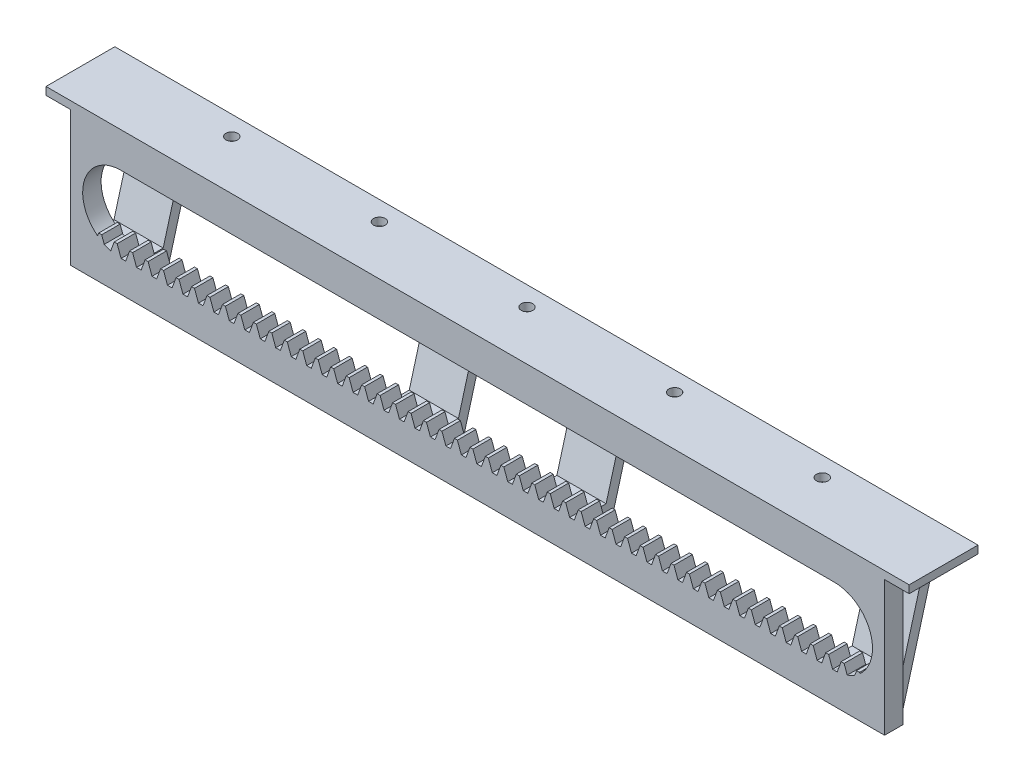
SolidWorks part; units mm, degrees
material "Nylon 101"
ref_plane "Front Plane" through (0, 0, 0) normal (0, 0, 1) x (1, 0, 0)
ref_plane "Top Plane" through (0, 0, 0) normal (0, 1, 0) x (1, 0, 0)
ref_plane "Right Plane" through (0, 0, 0) normal (1, 0, 0) x (0, 0, -1)
sketch "Sketch1" plane through (0, 0, 0) normal (0, 1, 0) x (1, 0, 0)
  line L0 (0, 0) -> (0, 4.7625)
  line L1 (0, 4.7625) -> (203.2, 4.7625)
  line L2 (203.2, 4.7625) -> (203.2, 0)
  line L3 (203.2, 0) -> (0, 0)
  dimension "D1" = 4.7625
  dimension "D2" = 203.2
extrude "Boss-Extrude1" add sketch "Sketch1" along normal blind 4.5
sketch "Sketch2" plane through (0, 0, 0) normal (0, 0, 1) x (1, 0, 0)
  line L0 (0, 3.2275) -> (203.2, 3.2275) construction
  line L1 (0, 4.5) -> (0, 0) construction
  line L2 (203.2, 4.5) -> (203.2, 0) construction
  line L3 (0, 1.7035) -> (203.2, 1.7035) construction
  line L4 (0, 4.5) -> (203.2, 4.5) construction
  line L5 (0, 4.5) -> (0.5952, 4.5) construction
  line L6 (0.5952, 4.5) -> (1.613, 1.7035)
  line L7 (1.613, 1.7035) -> (2.2082, 1.7035)
  line L8 (2.8034, 1.7035) -> (3.8212, 4.5)
  line L9 (3.8212, 4.5) -> (4.4164, 4.5) construction
  line L10 (2.2082, 1.7035) -> (2.8034, 1.7035)
  line L11 (0.5952, 4.5) -> (3.8212, 4.5)
  line L12 (4.5868, 4.5) -> (5.6047, 1.7035)
  line L13 (5.6047, 1.7035) -> (6.1999, 1.7035)
  line L14 (6.795, 1.7035) -> (7.8129, 4.5)
  line L15 (6.1999, 1.7035) -> (6.795, 1.7035)
  line L16 (4.5868, 4.5) -> (7.8129, 4.5)
  line L17 (3.9917, 4.5) -> (4.5868, 4.5) construction
  line L18 (7.8129, 4.5) -> (8.4081, 4.5) construction
  line L19 (8.5785, 4.5) -> (9.5964, 1.7035)
  line L20 (9.5964, 1.7035) -> (10.1915, 1.7035)
  line L21 (10.7867, 1.7035) -> (11.8046, 4.5)
  line L22 (10.1915, 1.7035) -> (10.7867, 1.7035)
  line L23 (8.5785, 4.5) -> (11.8046, 4.5)
  line L24 (7.9834, 4.5) -> (8.5785, 4.5) construction
  line L25 (11.8046, 4.5) -> (12.3997, 4.5) construction
  line L26 (12.5702, 4.5) -> (13.5881, 1.7035)
  line L27 (13.5881, 1.7035) -> (14.1832, 1.7035)
  line L28 (14.7784, 1.7035) -> (15.7962, 4.5)
  line L29 (14.1832, 1.7035) -> (14.7784, 1.7035)
  line L30 (12.5702, 4.5) -> (15.7962, 4.5)
  line L31 (11.975, 4.5) -> (12.5702, 4.5) construction
  line L32 (15.7962, 4.5) -> (16.3914, 4.5) construction
  line L33 (16.5619, 4.5) -> (17.5797, 1.7035)
  line L34 (17.5797, 1.7035) -> (18.1749, 1.7035)
  line L35 (18.7701, 1.7035) -> (19.7879, 4.5)
  line L36 (18.1749, 1.7035) -> (18.7701, 1.7035)
  line L37 (16.5619, 4.5) -> (19.7879, 4.5)
  line L38 (15.9667, 4.5) -> (16.5619, 4.5) construction
  line L39 (19.7879, 4.5) -> (20.3831, 4.5) construction
  line L40 (20.5535, 4.5) -> (21.5714, 1.7035)
  line L41 (21.5714, 1.7035) -> (22.1666, 1.7035)
  line L42 (22.7617, 1.7035) -> (23.7796, 4.5)
  line L43 (22.1666, 1.7035) -> (22.7617, 1.7035)
  line L44 (20.5535, 4.5) -> (23.7796, 4.5)
  line L45 (19.9584, 4.5) -> (20.5535, 4.5) construction
  line L46 (23.7796, 4.5) -> (24.3748, 4.5) construction
  line L47 (24.5452, 4.5) -> (25.5631, 1.7035)
  line L48 (25.5631, 1.7035) -> (26.1582, 1.7035)
  line L49 (26.7534, 1.7035) -> (27.7713, 4.5)
  line L50 (26.1582, 1.7035) -> (26.7534, 1.7035)
  line L51 (24.5452, 4.5) -> (27.7713, 4.5)
  line L52 (23.9501, 4.5) -> (24.5452, 4.5) construction
  line L53 (27.7713, 4.5) -> (28.3664, 4.5) construction
  line L54 (28.5369, 4.5) -> (29.5548, 1.7035)
  line L55 (29.5548, 1.7035) -> (30.1499, 1.7035)
  line L56 (30.7451, 1.7035) -> (31.763, 4.5)
  line L57 (30.1499, 1.7035) -> (30.7451, 1.7035)
  line L58 (28.5369, 4.5) -> (31.763, 4.5)
  line L59 (27.9417, 4.5) -> (28.5369, 4.5) construction
  line L60 (31.763, 4.5) -> (32.3581, 4.5) construction
  line L61 (32.5286, 4.5) -> (33.5464, 1.7035)
  line L62 (33.5464, 1.7035) -> (34.1416, 1.7035)
  line L63 (34.7368, 1.7035) -> (35.7546, 4.5)
  line L64 (34.1416, 1.7035) -> (34.7368, 1.7035)
  line L65 (32.5286, 4.5) -> (35.7546, 4.5)
  line L66 (31.9334, 4.5) -> (32.5286, 4.5) construction
  line L67 (35.7546, 4.5) -> (36.3498, 4.5) construction
  line L68 (36.5203, 4.5) -> (37.5381, 1.7035)
  line L69 (37.5381, 1.7035) -> (38.1333, 1.7035)
  line L70 (38.7284, 1.7035) -> (39.7463, 4.5)
  line L71 (38.1333, 1.7035) -> (38.7284, 1.7035)
  line L72 (36.5203, 4.5) -> (39.7463, 4.5)
  line L73 (35.9251, 4.5) -> (36.5203, 4.5) construction
  line L74 (39.7463, 4.5) -> (40.3415, 4.5) construction
  line L75 (40.5119, 4.5) -> (41.5298, 1.7035)
  line L76 (41.5298, 1.7035) -> (42.125, 1.7035)
  line L77 (42.7201, 1.7035) -> (43.738, 4.5)
  line L78 (42.125, 1.7035) -> (42.7201, 1.7035)
  line L79 (40.5119, 4.5) -> (43.738, 4.5)
  line L80 (39.9168, 4.5) -> (40.5119, 4.5) construction
  line L81 (43.738, 4.5) -> (44.3331, 4.5) construction
  line L82 (44.5036, 4.5) -> (45.5215, 1.7035)
  line L83 (45.5215, 1.7035) -> (46.1166, 1.7035)
  line L84 (46.7118, 1.7035) -> (47.7297, 4.5)
  line L85 (46.1166, 1.7035) -> (46.7118, 1.7035)
  line L86 (44.5036, 4.5) -> (47.7297, 4.5)
  line L87 (43.9084, 4.5) -> (44.5036, 4.5) construction
  line L88 (47.7297, 4.5) -> (48.3248, 4.5) construction
  line L89 (48.4953, 4.5) -> (49.5131, 1.7035)
  line L90 (49.5131, 1.7035) -> (50.1083, 1.7035)
  line L91 (50.7035, 1.7035) -> (51.7213, 4.5)
  line L92 (50.1083, 1.7035) -> (50.7035, 1.7035)
  line L93 (48.4953, 4.5) -> (51.7213, 4.5)
  line L94 (47.9001, 4.5) -> (48.4953, 4.5) construction
  line L95 (51.7213, 4.5) -> (52.3165, 4.5) construction
  line L96 (52.487, 4.5) -> (53.5048, 1.7035)
  line L97 (53.5048, 1.7035) -> (54.1, 1.7035)
  line L98 (54.6952, 1.7035) -> (55.713, 4.5)
  line L99 (54.1, 1.7035) -> (54.6952, 1.7035)
  line L100 (52.487, 4.5) -> (55.713, 4.5)
  line L101 (51.8918, 4.5) -> (52.487, 4.5) construction
  line L102 (55.713, 4.5) -> (56.3082, 4.5) construction
  line L103 (56.4786, 4.5) -> (57.4965, 1.7035)
  line L104 (57.4965, 1.7035) -> (58.0917, 1.7035)
  line L105 (58.6868, 1.7035) -> (59.7047, 4.5)
  line L106 (58.0917, 1.7035) -> (58.6868, 1.7035)
  line L107 (56.4786, 4.5) -> (59.7047, 4.5)
  line L108 (55.8835, 4.5) -> (56.4786, 4.5) construction
  line L109 (59.7047, 4.5) -> (60.2999, 4.5) construction
  line L110 (60.4703, 4.5) -> (61.4882, 1.7035)
  line L111 (61.4882, 1.7035) -> (62.0833, 1.7035)
  line L112 (62.6785, 1.7035) -> (63.6964, 4.5)
  line L113 (62.0833, 1.7035) -> (62.6785, 1.7035)
  line L114 (60.4703, 4.5) -> (63.6964, 4.5)
  line L115 (59.8751, 4.5) -> (60.4703, 4.5) construction
  line L116 (63.6964, 4.5) -> (64.2915, 4.5) construction
  line L117 (64.462, 4.5) -> (65.4798, 1.7035)
  line L118 (65.4798, 1.7035) -> (66.075, 1.7035)
  line L119 (66.6702, 1.7035) -> (67.688, 4.5)
  line L120 (66.075, 1.7035) -> (66.6702, 1.7035)
  line L121 (64.462, 4.5) -> (67.688, 4.5)
  line L122 (63.8668, 4.5) -> (64.462, 4.5) construction
  line L123 (67.688, 4.5) -> (68.2832, 4.5) construction
  line L124 (68.4537, 4.5) -> (69.4715, 1.7035)
  line L125 (69.4715, 1.7035) -> (70.0667, 1.7035)
  line L126 (70.6619, 1.7035) -> (71.6797, 4.5)
  line L127 (70.0667, 1.7035) -> (70.6619, 1.7035)
  line L128 (68.4537, 4.5) -> (71.6797, 4.5)
  line L129 (67.8585, 4.5) -> (68.4537, 4.5) construction
  line L130 (71.6797, 4.5) -> (72.2749, 4.5) construction
  line L131 (72.4453, 4.5) -> (73.4632, 1.7035)
  line L132 (73.4632, 1.7035) -> (74.0584, 1.7035)
  line L133 (74.6535, 1.7035) -> (75.6714, 4.5)
  line L134 (74.0584, 1.7035) -> (74.6535, 1.7035)
  line L135 (72.4453, 4.5) -> (75.6714, 4.5)
  line L136 (71.8502, 4.5) -> (72.4453, 4.5) construction
  line L137 (75.6714, 4.5) -> (76.2666, 4.5) construction
  line L138 (76.437, 4.5) -> (77.4549, 1.7035)
  line L139 (77.4549, 1.7035) -> (78.05, 1.7035)
  line L140 (78.6452, 1.7035) -> (79.6631, 4.5)
  line L141 (78.05, 1.7035) -> (78.6452, 1.7035)
  line L142 (76.437, 4.5) -> (79.6631, 4.5)
  line L143 (75.8418, 4.5) -> (76.437, 4.5) construction
  line L144 (79.6631, 4.5) -> (80.2582, 4.5) construction
  line L145 (80.4287, 4.5) -> (81.4465, 1.7035)
  line L146 (81.4465, 1.7035) -> (82.0417, 1.7035)
  line L147 (82.6369, 1.7035) -> (83.6547, 4.5)
  line L148 (82.0417, 1.7035) -> (82.6369, 1.7035)
  line L149 (80.4287, 4.5) -> (83.6547, 4.5)
  line L150 (79.8335, 4.5) -> (80.4287, 4.5) construction
  line L151 (83.6547, 4.5) -> (84.2499, 4.5) construction
  line L152 (84.4204, 4.5) -> (85.4382, 1.7035)
  line L153 (85.4382, 1.7035) -> (86.0334, 1.7035)
  line L154 (86.6286, 1.7035) -> (87.6464, 4.5)
  line L155 (86.0334, 1.7035) -> (86.6286, 1.7035)
  line L156 (84.4204, 4.5) -> (87.6464, 4.5)
  line L157 (83.8252, 4.5) -> (84.4204, 4.5) construction
  line L158 (87.6464, 4.5) -> (88.2416, 4.5) construction
  line L159 (88.412, 4.5) -> (89.4299, 1.7035)
  line L160 (89.4299, 1.7035) -> (90.0251, 1.7035)
  line L161 (90.6202, 1.7035) -> (91.6381, 4.5)
  line L162 (90.0251, 1.7035) -> (90.6202, 1.7035)
  line L163 (88.412, 4.5) -> (91.6381, 4.5)
  line L164 (87.8169, 4.5) -> (88.412, 4.5) construction
  line L165 (91.6381, 4.5) -> (92.2333, 4.5) construction
  line L166 (92.4037, 4.5) -> (93.4216, 1.7035)
  line L167 (93.4216, 1.7035) -> (94.0167, 1.7035)
  line L168 (94.6119, 1.7035) -> (95.6298, 4.5)
  line L169 (94.0167, 1.7035) -> (94.6119, 1.7035)
  line L170 (92.4037, 4.5) -> (95.6298, 4.5)
  line L171 (91.8086, 4.5) -> (92.4037, 4.5) construction
  line L172 (95.6298, 4.5) -> (96.2249, 4.5) construction
  line L173 (96.3954, 4.5) -> (97.4133, 1.7035)
  line L174 (97.4133, 1.7035) -> (98.0084, 1.7035)
  line L175 (98.6036, 1.7035) -> (99.6214, 4.5)
  line L176 (98.0084, 1.7035) -> (98.6036, 1.7035)
  line L177 (96.3954, 4.5) -> (99.6214, 4.5)
  line L178 (95.8002, 4.5) -> (96.3954, 4.5) construction
  line L179 (99.6214, 4.5) -> (100.2166, 4.5) construction
  line L180 (100.3871, 4.5) -> (101.4049, 1.7035)
  line L181 (101.4049, 1.7035) -> (102.0001, 1.7035)
  line L182 (102.5953, 1.7035) -> (103.6131, 4.5)
  line L183 (102.0001, 1.7035) -> (102.5953, 1.7035)
  line L184 (100.3871, 4.5) -> (103.6131, 4.5)
  line L185 (99.7919, 4.5) -> (100.3871, 4.5) construction
  line L186 (103.6131, 4.5) -> (104.2083, 4.5) construction
  line L187 (104.3787, 4.5) -> (105.3966, 1.7035)
  line L188 (105.3966, 1.7035) -> (105.9918, 1.7035)
  line L189 (106.5869, 1.7035) -> (107.6048, 4.5)
  line L190 (105.9918, 1.7035) -> (106.5869, 1.7035)
  line L191 (104.3787, 4.5) -> (107.6048, 4.5)
  line L192 (103.7836, 4.5) -> (104.3787, 4.5) construction
  line L193 (107.6048, 4.5) -> (108.2, 4.5) construction
  line L194 (108.3704, 4.5) -> (109.3883, 1.7035)
  line L195 (109.3883, 1.7035) -> (109.9835, 1.7035)
  line L196 (110.5786, 1.7035) -> (111.5965, 4.5)
  line L197 (109.9835, 1.7035) -> (110.5786, 1.7035)
  line L198 (108.3704, 4.5) -> (111.5965, 4.5)
  line L199 (107.7753, 4.5) -> (108.3704, 4.5) construction
  line L200 (111.5965, 4.5) -> (112.1916, 4.5) construction
  line L201 (112.3621, 4.5) -> (113.38, 1.7035)
  line L202 (113.38, 1.7035) -> (113.9751, 1.7035)
  line L203 (114.5703, 1.7035) -> (115.5882, 4.5)
  line L204 (113.9751, 1.7035) -> (114.5703, 1.7035)
  line L205 (112.3621, 4.5) -> (115.5882, 4.5)
  line L206 (111.7669, 4.5) -> (112.3621, 4.5) construction
  line L207 (115.5882, 4.5) -> (116.1833, 4.5) construction
  line L208 (116.3538, 4.5) -> (117.3716, 1.7035)
  line L209 (117.3716, 1.7035) -> (117.9668, 1.7035)
  line L210 (118.562, 1.7035) -> (119.5798, 4.5)
  line L211 (117.9668, 1.7035) -> (118.562, 1.7035)
  line L212 (116.3538, 4.5) -> (119.5798, 4.5)
  line L213 (115.7586, 4.5) -> (116.3538, 4.5) construction
  line L214 (119.5798, 4.5) -> (120.175, 4.5) construction
  line L215 (120.3455, 4.5) -> (121.3633, 1.7035)
  line L216 (121.3633, 1.7035) -> (121.9585, 1.7035)
  line L217 (122.5536, 1.7035) -> (123.5715, 4.5)
  line L218 (121.9585, 1.7035) -> (122.5536, 1.7035)
  line L219 (120.3455, 4.5) -> (123.5715, 4.5)
  line L220 (119.7503, 4.5) -> (120.3455, 4.5) construction
  line L221 (123.5715, 4.5) -> (124.1667, 4.5) construction
  line L222 (124.3371, 4.5) -> (125.355, 1.7035)
  line L223 (125.355, 1.7035) -> (125.9502, 1.7035)
  line L224 (126.5453, 1.7035) -> (127.5632, 4.5)
  line L225 (125.9502, 1.7035) -> (126.5453, 1.7035)
  line L226 (124.3371, 4.5) -> (127.5632, 4.5)
  line L227 (123.742, 4.5) -> (124.3371, 4.5) construction
  line L228 (127.5632, 4.5) -> (128.1583, 4.5) construction
  line L229 (128.3288, 4.5) -> (129.3467, 1.7035)
  line L230 (129.3467, 1.7035) -> (129.9418, 1.7035)
  line L231 (130.537, 1.7035) -> (131.5549, 4.5)
  line L232 (129.9418, 1.7035) -> (130.537, 1.7035)
  line L233 (128.3288, 4.5) -> (131.5549, 4.5)
  line L234 (127.7336, 4.5) -> (128.3288, 4.5) construction
  line L235 (131.5549, 4.5) -> (132.15, 4.5) construction
  line L236 (132.3205, 4.5) -> (133.3383, 1.7035)
  line L237 (133.3383, 1.7035) -> (133.9335, 1.7035)
  line L238 (134.5287, 1.7035) -> (135.5465, 4.5)
  line L239 (133.9335, 1.7035) -> (134.5287, 1.7035)
  line L240 (132.3205, 4.5) -> (135.5465, 4.5)
  line L241 (131.7253, 4.5) -> (132.3205, 4.5) construction
  line L242 (135.5465, 4.5) -> (136.1417, 4.5) construction
  line L243 (136.3122, 4.5) -> (137.33, 1.7035)
  line L244 (137.33, 1.7035) -> (137.9252, 1.7035)
  line L245 (138.5204, 1.7035) -> (139.5382, 4.5)
  line L246 (137.9252, 1.7035) -> (138.5204, 1.7035)
  line L247 (136.3122, 4.5) -> (139.5382, 4.5)
  line L248 (135.717, 4.5) -> (136.3122, 4.5) construction
  line L249 (139.5382, 4.5) -> (140.1334, 4.5) construction
  line L250 (140.3038, 4.5) -> (141.3217, 1.7035)
  line L251 (141.3217, 1.7035) -> (141.9169, 1.7035)
  line L252 (142.512, 1.7035) -> (143.5299, 4.5)
  line L253 (141.9169, 1.7035) -> (142.512, 1.7035)
  line L254 (140.3038, 4.5) -> (143.5299, 4.5)
  line L255 (139.7087, 4.5) -> (140.3038, 4.5) construction
  line L256 (143.5299, 4.5) -> (144.1251, 4.5) construction
  line L257 (144.2955, 4.5) -> (145.3134, 1.7035)
  line L258 (145.3134, 1.7035) -> (145.9085, 1.7035)
  line L259 (146.5037, 1.7035) -> (147.5216, 4.5)
  line L260 (145.9085, 1.7035) -> (146.5037, 1.7035)
  line L261 (144.2955, 4.5) -> (147.5216, 4.5)
  line L262 (143.7003, 4.5) -> (144.2955, 4.5) construction
  line L263 (147.5216, 4.5) -> (148.1167, 4.5) construction
  line L264 (148.2872, 4.5) -> (149.305, 1.7035)
  line L265 (149.305, 1.7035) -> (149.9002, 1.7035)
  line L266 (150.4954, 1.7035) -> (151.5132, 4.5)
  line L267 (149.9002, 1.7035) -> (150.4954, 1.7035)
  line L268 (148.2872, 4.5) -> (151.5132, 4.5)
  line L269 (147.692, 4.5) -> (148.2872, 4.5) construction
  line L270 (151.5132, 4.5) -> (152.1084, 4.5) construction
  line L271 (152.2789, 4.5) -> (153.2967, 1.7035)
  line L272 (153.2967, 1.7035) -> (153.8919, 1.7035)
  line L273 (154.4871, 1.7035) -> (155.5049, 4.5)
  line L274 (153.8919, 1.7035) -> (154.4871, 1.7035)
  line L275 (152.2789, 4.5) -> (155.5049, 4.5)
  line L276 (151.6837, 4.5) -> (152.2789, 4.5) construction
  line L277 (155.5049, 4.5) -> (156.1001, 4.5) construction
  line L278 (156.2705, 4.5) -> (157.2884, 1.7035)
  line L279 (157.2884, 1.7035) -> (157.8836, 1.7035)
  line L280 (158.4787, 1.7035) -> (159.4966, 4.5)
  line L281 (157.8836, 1.7035) -> (158.4787, 1.7035)
  line L282 (156.2705, 4.5) -> (159.4966, 4.5)
  line L283 (155.6754, 4.5) -> (156.2705, 4.5) construction
  line L284 (159.4966, 4.5) -> (160.0918, 4.5) construction
  line L285 (160.2622, 4.5) -> (161.2801, 1.7035)
  line L286 (161.2801, 1.7035) -> (161.8752, 1.7035)
  line L287 (162.4704, 1.7035) -> (163.4883, 4.5)
  line L288 (161.8752, 1.7035) -> (162.4704, 1.7035)
  line L289 (160.2622, 4.5) -> (163.4883, 4.5)
  line L290 (159.667, 4.5) -> (160.2622, 4.5) construction
  line L291 (163.4883, 4.5) -> (164.0834, 4.5) construction
  line L292 (164.2539, 4.5) -> (165.2718, 1.7035)
  line L293 (165.2718, 1.7035) -> (165.8669, 1.7035)
  line L294 (166.4621, 1.7035) -> (167.4799, 4.5)
  line L295 (165.8669, 1.7035) -> (166.4621, 1.7035)
  line L296 (164.2539, 4.5) -> (167.4799, 4.5)
  line L297 (163.6587, 4.5) -> (164.2539, 4.5) construction
  line L298 (167.4799, 4.5) -> (168.0751, 4.5) construction
  line L299 (168.2456, 4.5) -> (169.2634, 1.7035)
  line L300 (169.2634, 1.7035) -> (169.8586, 1.7035)
  line L301 (170.4538, 1.7035) -> (171.4716, 4.5)
  line L302 (169.8586, 1.7035) -> (170.4538, 1.7035)
  line L303 (168.2456, 4.5) -> (171.4716, 4.5)
  line L304 (167.6504, 4.5) -> (168.2456, 4.5) construction
  line L305 (171.4716, 4.5) -> (172.0668, 4.5) construction
  line L306 (172.2372, 4.5) -> (173.2551, 1.7035)
  line L307 (173.2551, 1.7035) -> (173.8503, 1.7035)
  line L308 (174.4454, 1.7035) -> (175.4633, 4.5)
  line L309 (173.8503, 1.7035) -> (174.4454, 1.7035)
  line L310 (172.2372, 4.5) -> (175.4633, 4.5)
  line L311 (171.6421, 4.5) -> (172.2372, 4.5) construction
  line L312 (175.4633, 4.5) -> (176.0585, 4.5) construction
  line L313 (176.2289, 4.5) -> (177.2468, 1.7035)
  line L314 (177.2468, 1.7035) -> (177.8419, 1.7035)
  line L315 (178.4371, 1.7035) -> (179.455, 4.5)
  line L316 (177.8419, 1.7035) -> (178.4371, 1.7035)
  line L317 (176.2289, 4.5) -> (179.455, 4.5)
  line L318 (175.6338, 4.5) -> (176.2289, 4.5) construction
  line L319 (179.455, 4.5) -> (180.0501, 4.5) construction
  line L320 (180.2206, 4.5) -> (181.2385, 1.7035)
  line L321 (181.2385, 1.7035) -> (181.8336, 1.7035)
  line L322 (182.4288, 1.7035) -> (183.4466, 4.5)
  line L323 (181.8336, 1.7035) -> (182.4288, 1.7035)
  line L324 (180.2206, 4.5) -> (183.4466, 4.5)
  line L325 (179.6254, 4.5) -> (180.2206, 4.5) construction
  line L326 (183.4466, 4.5) -> (184.0418, 4.5) construction
  line L327 (184.2123, 4.5) -> (185.2301, 1.7035)
  line L328 (185.2301, 1.7035) -> (185.8253, 1.7035)
  line L329 (186.4205, 1.7035) -> (187.4383, 4.5)
  line L330 (185.8253, 1.7035) -> (186.4205, 1.7035)
  line L331 (184.2123, 4.5) -> (187.4383, 4.5)
  line L332 (183.6171, 4.5) -> (184.2123, 4.5) construction
  line L333 (187.4383, 4.5) -> (188.0335, 4.5) construction
  line L334 (188.204, 4.5) -> (189.2218, 1.7035)
  line L335 (189.2218, 1.7035) -> (189.817, 1.7035)
  line L336 (190.4121, 1.7035) -> (191.43, 4.5)
  line L337 (189.817, 1.7035) -> (190.4121, 1.7035)
  line L338 (188.204, 4.5) -> (191.43, 4.5)
  line L339 (187.6088, 4.5) -> (188.204, 4.5) construction
  line L340 (191.43, 4.5) -> (192.0252, 4.5) construction
  line L341 (192.1956, 4.5) -> (193.2135, 1.7035)
  line L342 (193.2135, 1.7035) -> (193.8087, 1.7035)
  line L343 (194.4038, 1.7035) -> (195.4217, 4.5)
  line L344 (193.8087, 1.7035) -> (194.4038, 1.7035)
  line L345 (192.1956, 4.5) -> (195.4217, 4.5)
  line L346 (191.6005, 4.5) -> (192.1956, 4.5) construction
  line L347 (195.4217, 4.5) -> (196.0168, 4.5) construction
  line L348 (196.1873, 4.5) -> (197.2052, 1.7035)
  line L349 (197.2052, 1.7035) -> (197.8003, 1.7035)
  line L350 (198.3955, 1.7035) -> (199.4134, 4.5)
  line L351 (197.8003, 1.7035) -> (198.3955, 1.7035)
  line L352 (196.1873, 4.5) -> (199.4134, 4.5)
  line L353 (195.5921, 4.5) -> (196.1873, 4.5) construction
  line L354 (199.4134, 4.5) -> (200.0085, 4.5) construction
  line L355 (200.179, 4.5) -> (201.1968, 1.7035)
  line L356 (201.1968, 1.7035) -> (201.792, 1.7035)
  line L357 (202.3872, 1.7035) -> (203.405, 4.5)
  line L358 (201.792, 1.7035) -> (202.3872, 1.7035)
  line L359 (200.179, 4.5) -> (203.405, 4.5)
  line L360 (199.5838, 4.5) -> (200.179, 4.5) construction
  line L361 (203.405, 4.5) -> (204.0002, 4.5) construction
  line L362 (204.1707, 4.5) -> (205.1885, 1.7035)
  line L363 (205.1885, 1.7035) -> (205.7837, 1.7035)
  line L364 (206.3788, 1.7035) -> (207.3967, 4.5)
  line L365 (205.7837, 1.7035) -> (206.3788, 1.7035)
  line L366 (204.1707, 4.5) -> (207.3967, 4.5)
  line L367 (203.5755, 4.5) -> (204.1707, 4.5) construction
  line L368 (207.3967, 4.5) -> (207.9919, 4.5) construction
  line L369 (208.1623, 4.5) -> (209.1802, 1.7035)
  line L370 (209.1802, 1.7035) -> (209.7754, 1.7035)
  line L371 (210.3705, 1.7035) -> (211.3884, 4.5)
  line L372 (209.7754, 1.7035) -> (210.3705, 1.7035)
  line L373 (208.1623, 4.5) -> (211.3884, 4.5)
  line L374 (207.5672, 4.5) -> (208.1623, 4.5) construction
  line L375 (211.3884, 4.5) -> (211.9835, 4.5) construction
  line L376 (212.154, 4.5) -> (213.1719, 1.7035)
  line L377 (213.1719, 1.7035) -> (213.767, 1.7035)
  line L378 (214.3622, 1.7035) -> (215.3801, 4.5)
  line L379 (213.767, 1.7035) -> (214.3622, 1.7035)
  line L380 (212.154, 4.5) -> (215.3801, 4.5)
  line L381 (211.5588, 4.5) -> (212.154, 4.5) construction
  line L382 (215.3801, 4.5) -> (215.9752, 4.5) construction
  line L383 (216.1457, 4.5) -> (217.1635, 1.7035)
  line L384 (217.1635, 1.7035) -> (217.7587, 1.7035)
  line L385 (218.3539, 1.7035) -> (219.3717, 4.5)
  line L386 (217.7587, 1.7035) -> (218.3539, 1.7035)
  line L387 (216.1457, 4.5) -> (219.3717, 4.5)
  line L388 (215.5505, 4.5) -> (216.1457, 4.5) construction
  line L389 (219.3717, 4.5) -> (219.9669, 4.5) construction
  line L390 (220.1374, 4.5) -> (221.1552, 1.7035)
  line L391 (221.1552, 1.7035) -> (221.7504, 1.7035)
  line L392 (222.3456, 1.7035) -> (223.3634, 4.5)
  line L393 (221.7504, 1.7035) -> (222.3456, 1.7035)
  line L394 (220.1374, 4.5) -> (223.3634, 4.5)
  line L395 (219.5422, 4.5) -> (220.1374, 4.5) construction
  line L396 (223.3634, 4.5) -> (223.9586, 4.5) construction
  line L397 (224.129, 4.5) -> (225.1469, 1.7035)
  line L398 (225.1469, 1.7035) -> (225.7421, 1.7035)
  line L399 (226.3372, 1.7035) -> (227.3551, 4.5)
  line L400 (225.7421, 1.7035) -> (226.3372, 1.7035)
  line L401 (224.129, 4.5) -> (227.3551, 4.5)
  line L402 (223.5339, 4.5) -> (224.129, 4.5) construction
  line L403 (227.3551, 4.5) -> (227.9503, 4.5) construction
  line L404 (228.1207, 4.5) -> (229.1386, 1.7035)
  line L405 (229.1386, 1.7035) -> (229.7337, 1.7035)
  line L406 (230.3289, 1.7035) -> (231.3468, 4.5)
  line L407 (229.7337, 1.7035) -> (230.3289, 1.7035)
  line L408 (228.1207, 4.5) -> (231.3468, 4.5)
  line L409 (227.5255, 4.5) -> (228.1207, 4.5) construction
  line L410 (231.3468, 4.5) -> (231.9419, 4.5) construction
  line L411 (232.1124, 4.5) -> (233.1302, 1.7035)
  line L412 (233.1302, 1.7035) -> (233.7254, 1.7035)
  line L413 (234.3206, 1.7035) -> (235.3384, 4.5)
  line L414 (233.7254, 1.7035) -> (234.3206, 1.7035)
  line L415 (232.1124, 4.5) -> (235.3384, 4.5)
  line L416 (231.5172, 4.5) -> (232.1124, 4.5) construction
  line L417 (235.3384, 4.5) -> (235.9336, 4.5) construction
  line L418 (236.1041, 4.5) -> (237.1219, 1.7035)
  line L419 (237.1219, 1.7035) -> (237.7171, 1.7035)
  line L420 (238.3123, 1.7035) -> (239.3301, 4.5)
  line L421 (237.7171, 1.7035) -> (238.3123, 1.7035)
  line L422 (236.1041, 4.5) -> (239.3301, 4.5)
  line L423 (235.5089, 4.5) -> (236.1041, 4.5) construction
  line L424 (239.3301, 4.5) -> (239.9253, 4.5) construction
  line L425 (240.0957, 4.5) -> (241.1136, 1.7035)
  line L426 (241.1136, 1.7035) -> (241.7088, 1.7035)
  line L427 (242.3039, 1.7035) -> (243.3218, 4.5)
  line L428 (241.7088, 1.7035) -> (242.3039, 1.7035)
  line L429 (240.0957, 4.5) -> (243.3218, 4.5)
  line L430 (239.5006, 4.5) -> (240.0957, 4.5) construction
  line L431 (243.3218, 4.5) -> (243.917, 4.5) construction
  line L432 (244.0874, 4.5) -> (245.1053, 1.7035)
  line L433 (245.1053, 1.7035) -> (245.7004, 1.7035)
  line L434 (246.2956, 1.7035) -> (247.3135, 4.5)
  line L435 (245.7004, 1.7035) -> (246.2956, 1.7035)
  line L436 (244.0874, 4.5) -> (247.3135, 4.5)
  line L437 (243.4923, 4.5) -> (244.0874, 4.5) construction
  line L438 (247.3135, 4.5) -> (247.9086, 4.5) construction
  line L439 (248.0791, 4.5) -> (249.097, 1.7035)
  line L440 (249.097, 1.7035) -> (249.6921, 1.7035)
  line L441 (250.2873, 1.7035) -> (251.3051, 4.5)
  line L442 (249.6921, 1.7035) -> (250.2873, 1.7035)
  line L443 (248.0791, 4.5) -> (251.3051, 4.5)
  line L444 (247.4839, 4.5) -> (248.0791, 4.5) construction
  line L445 (251.3051, 4.5) -> (251.9003, 4.5) construction
  line L446 (252.0708, 4.5) -> (253.0886, 1.7035)
  line L447 (253.0886, 1.7035) -> (253.6838, 1.7035)
  line L448 (254.279, 1.7035) -> (255.2968, 4.5)
  line L449 (253.6838, 1.7035) -> (254.279, 1.7035)
  line L450 (252.0708, 4.5) -> (255.2968, 4.5)
  line L451 (251.4756, 4.5) -> (252.0708, 4.5) construction
  line L452 (255.2968, 4.5) -> (255.892, 4.5) construction
  line L453 (256.0624, 4.5) -> (257.0803, 1.7035)
  line L454 (257.0803, 1.7035) -> (257.6755, 1.7035)
  line L455 (258.2706, 1.7035) -> (259.2885, 4.5)
  line L456 (257.6755, 1.7035) -> (258.2706, 1.7035)
  line L457 (256.0624, 4.5) -> (259.2885, 4.5)
  line L458 (255.4673, 4.5) -> (256.0624, 4.5) construction
  line L459 (259.2885, 4.5) -> (259.8837, 4.5) construction
  line L460 (260.0541, 4.5) -> (261.072, 1.7035)
  line L461 (261.072, 1.7035) -> (261.6671, 1.7035)
  line L462 (262.2623, 1.7035) -> (263.2802, 4.5)
  line L463 (261.6671, 1.7035) -> (262.2623, 1.7035)
  line L464 (260.0541, 4.5) -> (263.2802, 4.5)
  line L465 (259.459, 4.5) -> (260.0541, 4.5) construction
  line L466 (263.2802, 4.5) -> (263.8753, 4.5) construction
  line L467 (264.0458, 4.5) -> (265.0637, 1.7035)
  line L468 (265.0637, 1.7035) -> (265.6588, 1.7035)
  line L469 (266.254, 1.7035) -> (267.2718, 4.5)
  line L470 (265.6588, 1.7035) -> (266.254, 1.7035)
  line L471 (264.0458, 4.5) -> (267.2718, 4.5)
  line L472 (263.4506, 4.5) -> (264.0458, 4.5) construction
  line L473 (267.2718, 4.5) -> (267.867, 4.5) construction
  line L474 (268.0375, 4.5) -> (269.0553, 1.7035)
  line L475 (269.0553, 1.7035) -> (269.6505, 1.7035)
  line L476 (270.2457, 1.7035) -> (271.2635, 4.5)
  line L477 (269.6505, 1.7035) -> (270.2457, 1.7035)
  line L478 (268.0375, 4.5) -> (271.2635, 4.5)
  line L479 (267.4423, 4.5) -> (268.0375, 4.5) construction
  line L480 (271.2635, 4.5) -> (271.8587, 4.5) construction
  line L481 (272.0292, 4.5) -> (273.047, 1.7035)
  line L482 (273.047, 1.7035) -> (273.6422, 1.7035)
  line L483 (274.2373, 1.7035) -> (275.2552, 4.5)
  line L484 (273.6422, 1.7035) -> (274.2373, 1.7035)
  line L485 (272.0292, 4.5) -> (275.2552, 4.5)
  line L486 (271.434, 4.5) -> (272.0292, 4.5) construction
  line L487 (275.2552, 4.5) -> (275.8504, 4.5) construction
  line L488 (276.0208, 4.5) -> (277.0387, 1.7035)
  line L489 (277.0387, 1.7035) -> (277.6339, 1.7035)
  line L490 (278.229, 1.7035) -> (279.2469, 4.5)
  line L491 (277.6339, 1.7035) -> (278.229, 1.7035)
  line L492 (276.0208, 4.5) -> (279.2469, 4.5)
  line L493 (275.4257, 4.5) -> (276.0208, 4.5) construction
  line L494 (279.2469, 4.5) -> (279.842, 4.5) construction
  line L495 (280.0125, 4.5) -> (281.0304, 1.7035)
  line L496 (281.0304, 1.7035) -> (281.6255, 1.7035)
  line L497 (282.2207, 1.7035) -> (283.2386, 4.5)
  line L498 (281.6255, 1.7035) -> (282.2207, 1.7035)
  line L499 (280.0125, 4.5) -> (283.2386, 4.5)
  line L500 (279.4173, 4.5) -> (280.0125, 4.5) construction
  line L501 (283.2386, 4.5) -> (283.8337, 4.5) construction
  line L502 (284.0042, 4.5) -> (285.022, 1.7035)
  line L503 (285.022, 1.7035) -> (285.6172, 1.7035)
  line L504 (286.2124, 1.7035) -> (287.2302, 4.5)
  line L505 (285.6172, 1.7035) -> (286.2124, 1.7035)
  line L506 (284.0042, 4.5) -> (287.2302, 4.5)
  line L507 (283.409, 4.5) -> (284.0042, 4.5) construction
  line L508 (287.2302, 4.5) -> (287.8254, 4.5) construction
  line L509 (287.9959, 4.5) -> (289.0137, 1.7035)
  line L510 (289.0137, 1.7035) -> (289.6089, 1.7035)
  line L511 (290.204, 1.7035) -> (291.2219, 4.5)
  line L512 (289.6089, 1.7035) -> (290.204, 1.7035)
  line L513 (287.9959, 4.5) -> (291.2219, 4.5)
  line L514 (287.4007, 4.5) -> (287.9959, 4.5) construction
  line L515 (291.2219, 4.5) -> (291.8171, 4.5) construction
  line L516 (291.9875, 4.5) -> (293.0054, 1.7035)
  line L517 (293.0054, 1.7035) -> (293.6006, 1.7035)
  line L518 (294.1957, 1.7035) -> (295.2136, 4.5)
  line L519 (293.6006, 1.7035) -> (294.1957, 1.7035)
  line L520 (291.9875, 4.5) -> (295.2136, 4.5)
  line L521 (291.3924, 4.5) -> (291.9875, 4.5) construction
  line L522 (295.2136, 4.5) -> (295.8087, 4.5) construction
  line L523 (295.9792, 4.5) -> (296.9971, 1.7035)
  line L524 (296.9971, 1.7035) -> (297.5922, 1.7035)
  line L525 (298.1874, 1.7035) -> (299.2053, 4.5)
  line L526 (297.5922, 1.7035) -> (298.1874, 1.7035)
  line L527 (295.9792, 4.5) -> (299.2053, 4.5)
  line L528 (295.384, 4.5) -> (295.9792, 4.5) construction
  line L529 (299.2053, 4.5) -> (299.8004, 4.5) construction
  line L530 (299.9709, 4.5) -> (300.9887, 1.7035)
  line L531 (300.9887, 1.7035) -> (301.5839, 1.7035)
  line L532 (302.1791, 1.7035) -> (303.1969, 4.5)
  line L533 (301.5839, 1.7035) -> (302.1791, 1.7035)
  line L534 (299.9709, 4.5) -> (303.1969, 4.5)
  line L535 (299.3757, 4.5) -> (299.9709, 4.5) construction
  line L536 (303.1969, 4.5) -> (303.7921, 4.5) construction
  line L537 (303.9626, 4.5) -> (304.9804, 1.7035)
  line L538 (304.9804, 1.7035) -> (305.5756, 1.7035)
  line L539 (306.1708, 1.7035) -> (307.1886, 4.5)
  line L540 (305.5756, 1.7035) -> (306.1708, 1.7035)
  line L541 (303.9626, 4.5) -> (307.1886, 4.5)
  line L542 (303.3674, 4.5) -> (303.9626, 4.5) construction
  line L543 (307.1886, 4.5) -> (307.7838, 4.5) construction
  line L544 (307.9542, 4.5) -> (308.9721, 1.7035)
  line L545 (308.9721, 1.7035) -> (309.5673, 1.7035)
  line L546 (310.1624, 1.7035) -> (311.1803, 4.5)
  line L547 (309.5673, 1.7035) -> (310.1624, 1.7035)
  line L548 (307.9542, 4.5) -> (311.1803, 4.5)
  line L549 (307.3591, 4.5) -> (307.9542, 4.5) construction
  line L550 (311.1803, 4.5) -> (311.7755, 4.5) construction
  line L551 (311.9459, 4.5) -> (312.9638, 1.7035)
  line L552 (312.9638, 1.7035) -> (313.5589, 1.7035)
  line L553 (314.1541, 1.7035) -> (315.172, 4.5)
  line L554 (313.5589, 1.7035) -> (314.1541, 1.7035)
  line L555 (311.9459, 4.5) -> (315.172, 4.5)
  line L556 (311.3507, 4.5) -> (311.9459, 4.5) construction
  line L557 (315.172, 4.5) -> (315.7671, 4.5) construction
  line L558 (315.9376, 4.5) -> (316.9554, 1.7035)
  line L559 (316.9554, 1.7035) -> (317.5506, 1.7035)
  line L560 (318.1458, 1.7035) -> (319.1636, 4.5)
  line L561 (317.5506, 1.7035) -> (318.1458, 1.7035)
  line L562 (315.9376, 4.5) -> (319.1636, 4.5)
  line L563 (315.3424, 4.5) -> (315.9376, 4.5) construction
  line L564 (319.1636, 4.5) -> (319.7588, 4.5) construction
  line L565 (319.9293, 4.5) -> (320.9471, 1.7035)
  line L566 (320.9471, 1.7035) -> (321.5423, 1.7035)
  line L567 (322.1375, 1.7035) -> (323.1553, 4.5)
  line L568 (321.5423, 1.7035) -> (322.1375, 1.7035)
  line L569 (319.9293, 4.5) -> (323.1553, 4.5)
  line L570 (319.3341, 4.5) -> (319.9293, 4.5) construction
  line L571 (323.1553, 4.5) -> (323.7505, 4.5) construction
  line L572 (323.9209, 4.5) -> (324.9388, 1.7035)
  line L573 (324.9388, 1.7035) -> (325.534, 1.7035)
  line L574 (326.1291, 1.7035) -> (327.147, 4.5)
  line L575 (325.534, 1.7035) -> (326.1291, 1.7035)
  line L576 (323.9209, 4.5) -> (327.147, 4.5)
  line L577 (323.3258, 4.5) -> (323.9209, 4.5) construction
  line L578 (327.147, 4.5) -> (327.7422, 4.5) construction
  line L579 (327.9126, 4.5) -> (328.9305, 1.7035)
  line L580 (328.9305, 1.7035) -> (329.5256, 1.7035)
  line L581 (330.1208, 1.7035) -> (331.1387, 4.5)
  line L582 (329.5256, 1.7035) -> (330.1208, 1.7035)
  line L583 (327.9126, 4.5) -> (331.1387, 4.5)
  line L584 (327.3175, 4.5) -> (327.9126, 4.5) construction
  line L585 (331.1387, 4.5) -> (331.7338, 4.5) construction
  line L586 (331.9043, 4.5) -> (332.9222, 1.7035)
  line L587 (332.9222, 1.7035) -> (333.5173, 1.7035)
  line L588 (334.1125, 1.7035) -> (335.1303, 4.5)
  line L589 (333.5173, 1.7035) -> (334.1125, 1.7035)
  line L590 (331.9043, 4.5) -> (335.1303, 4.5)
  line L591 (331.3091, 4.5) -> (331.9043, 4.5) construction
  line L592 (335.1303, 4.5) -> (335.7255, 4.5) construction
  line L593 (335.896, 4.5) -> (336.9138, 1.7035)
  line L594 (336.9138, 1.7035) -> (337.509, 1.7035)
  line L595 (338.1042, 1.7035) -> (339.122, 4.5)
  line L596 (337.509, 1.7035) -> (338.1042, 1.7035)
  line L597 (335.896, 4.5) -> (339.122, 4.5)
  line L598 (335.3008, 4.5) -> (335.896, 4.5) construction
  line L599 (339.122, 4.5) -> (339.7172, 4.5) construction
  line L600 (339.8876, 4.5) -> (340.9055, 1.7035)
  line L601 (340.9055, 1.7035) -> (341.5007, 1.7035)
  line L602 (342.0958, 1.7035) -> (343.1137, 4.5)
  line L603 (341.5007, 1.7035) -> (342.0958, 1.7035)
  line L604 (339.8876, 4.5) -> (343.1137, 4.5)
  line L605 (339.2925, 4.5) -> (339.8876, 4.5) construction
  line L606 (343.1137, 4.5) -> (343.7089, 4.5) construction
  line L607 (343.8793, 4.5) -> (344.8972, 1.7035)
  line L608 (344.8972, 1.7035) -> (345.4923, 1.7035)
  line L609 (346.0875, 1.7035) -> (347.1054, 4.5)
  line L610 (345.4923, 1.7035) -> (346.0875, 1.7035)
  line L611 (343.8793, 4.5) -> (347.1054, 4.5)
  line L612 (343.2842, 4.5) -> (343.8793, 4.5) construction
  line L613 (347.1054, 4.5) -> (347.7005, 4.5) construction
  line L614 (347.871, 4.5) -> (348.8889, 1.7035)
  line L615 (348.8889, 1.7035) -> (349.484, 1.7035)
  line L616 (350.0792, 1.7035) -> (351.097, 4.5)
  line L617 (349.484, 1.7035) -> (350.0792, 1.7035)
  line L618 (347.871, 4.5) -> (351.097, 4.5)
  line L619 (347.2758, 4.5) -> (347.871, 4.5) construction
  line L620 (351.097, 4.5) -> (351.6922, 4.5) construction
  line L621 (351.8627, 4.5) -> (352.8805, 1.7035)
  line L622 (352.8805, 1.7035) -> (353.4757, 1.7035)
  line L623 (354.0709, 1.7035) -> (355.0887, 4.5)
  line L624 (353.4757, 1.7035) -> (354.0709, 1.7035)
  line L625 (351.8627, 4.5) -> (355.0887, 4.5)
  line L626 (351.2675, 4.5) -> (351.8627, 4.5) construction
  line L627 (355.0887, 4.5) -> (355.6839, 4.5) construction
  line L628 (355.8544, 4.5) -> (356.8722, 1.7035)
  line L629 (356.8722, 1.7035) -> (357.4674, 1.7035)
  line L630 (358.0625, 1.7035) -> (359.0804, 4.5)
  line L631 (357.4674, 1.7035) -> (358.0625, 1.7035)
  line L632 (355.8544, 4.5) -> (359.0804, 4.5)
  line L633 (355.2592, 4.5) -> (355.8544, 4.5) construction
  line L634 (359.0804, 4.5) -> (359.6756, 4.5) construction
  line L635 (359.846, 4.5) -> (360.8639, 1.7035)
  line L636 (360.8639, 1.7035) -> (361.4591, 1.7035)
  line L637 (362.0542, 1.7035) -> (363.0721, 4.5)
  line L638 (361.4591, 1.7035) -> (362.0542, 1.7035)
  line L639 (359.846, 4.5) -> (363.0721, 4.5)
  line L640 (359.2509, 4.5) -> (359.846, 4.5) construction
  line L641 (363.0721, 4.5) -> (363.6672, 4.5) construction
  line L642 (363.8377, 4.5) -> (364.8556, 1.7035)
  line L643 (364.8556, 1.7035) -> (365.4507, 1.7035)
  line L644 (366.0459, 1.7035) -> (367.0638, 4.5)
  line L645 (365.4507, 1.7035) -> (366.0459, 1.7035)
  line L646 (363.8377, 4.5) -> (367.0638, 4.5)
  line L647 (363.2425, 4.5) -> (363.8377, 4.5) construction
  line L648 (367.0638, 4.5) -> (367.6589, 4.5) construction
  line L649 (367.8294, 4.5) -> (368.8472, 1.7035)
  line L650 (368.8472, 1.7035) -> (369.4424, 1.7035)
  line L651 (370.0376, 1.7035) -> (371.0554, 4.5)
  line L652 (369.4424, 1.7035) -> (370.0376, 1.7035)
  line L653 (367.8294, 4.5) -> (371.0554, 4.5)
  line L654 (367.2342, 4.5) -> (367.8294, 4.5) construction
  line L655 (371.0554, 4.5) -> (371.6506, 4.5) construction
  line L656 (371.8211, 4.5) -> (372.8389, 1.7035)
  line L657 (372.8389, 1.7035) -> (373.4341, 1.7035)
  line L658 (374.0292, 1.7035) -> (375.0471, 4.5)
  line L659 (373.4341, 1.7035) -> (374.0292, 1.7035)
  line L660 (371.8211, 4.5) -> (375.0471, 4.5)
  line L661 (371.2259, 4.5) -> (371.8211, 4.5) construction
  line L662 (375.0471, 4.5) -> (375.6423, 4.5) construction
  line L663 (375.8127, 4.5) -> (376.8306, 1.7035)
  line L664 (376.8306, 1.7035) -> (377.4258, 1.7035)
  line L665 (378.0209, 1.7035) -> (379.0388, 4.5)
  line L666 (377.4258, 1.7035) -> (378.0209, 1.7035)
  line L667 (375.8127, 4.5) -> (379.0388, 4.5)
  line L668 (375.2176, 4.5) -> (375.8127, 4.5) construction
  line L669 (379.0388, 4.5) -> (379.6339, 4.5) construction
  line L670 (379.8044, 4.5) -> (380.8223, 1.7035)
  line L671 (380.8223, 1.7035) -> (381.4174, 1.7035)
  line L672 (382.0126, 1.7035) -> (383.0305, 4.5)
  line L673 (381.4174, 1.7035) -> (382.0126, 1.7035)
  line L674 (379.8044, 4.5) -> (383.0305, 4.5)
  line L675 (379.2092, 4.5) -> (379.8044, 4.5) construction
  line L676 (383.0305, 4.5) -> (383.6256, 4.5) construction
  line L677 (383.7961, 4.5) -> (384.8139, 1.7035)
  line L678 (384.8139, 1.7035) -> (385.4091, 1.7035)
  line L679 (386.0043, 1.7035) -> (387.0221, 4.5)
  line L680 (385.4091, 1.7035) -> (386.0043, 1.7035)
  line L681 (383.7961, 4.5) -> (387.0221, 4.5)
  line L682 (383.2009, 4.5) -> (383.7961, 4.5) construction
  line L683 (387.0221, 4.5) -> (387.6173, 4.5) construction
  line L684 (387.7878, 4.5) -> (388.8056, 1.7035)
  line L685 (388.8056, 1.7035) -> (389.4008, 1.7035)
  line L686 (389.996, 1.7035) -> (391.0138, 4.5)
  line L687 (389.4008, 1.7035) -> (389.996, 1.7035)
  line L688 (387.7878, 4.5) -> (391.0138, 4.5)
  line L689 (387.1926, 4.5) -> (387.7878, 4.5) construction
  line L690 (391.0138, 4.5) -> (391.609, 4.5) construction
  line L691 (391.7794, 4.5) -> (392.7973, 1.7035)
  line L692 (392.7973, 1.7035) -> (393.3925, 1.7035)
  line L693 (393.9876, 1.7035) -> (395.0055, 4.5)
  line L694 (393.3925, 1.7035) -> (393.9876, 1.7035)
  line L695 (391.7794, 4.5) -> (395.0055, 4.5)
  line L696 (391.1843, 4.5) -> (391.7794, 4.5) construction
  line L697 (395.0055, 4.5) -> (395.6007, 4.5) construction
  line L698 (395.7711, 4.5) -> (396.789, 1.7035)
  line L699 (396.789, 1.7035) -> (397.3841, 1.7035)
  line L700 (397.9793, 1.7035) -> (398.9972, 4.5)
  line L701 (397.3841, 1.7035) -> (397.9793, 1.7035)
  line L702 (395.7711, 4.5) -> (398.9972, 4.5)
  line L703 (395.1759, 4.5) -> (395.7711, 4.5) construction
  line L704 (398.9972, 4.5) -> (399.5923, 4.5) construction
  line L705 (399.7628, 4.5) -> (400.7806, 1.7035)
  line L706 (400.7806, 1.7035) -> (401.3758, 1.7035)
  line L707 (401.971, 1.7035) -> (402.9888, 4.5)
  line L708 (401.3758, 1.7035) -> (401.971, 1.7035)
  line L709 (399.7628, 4.5) -> (402.9888, 4.5)
  line L710 (399.1676, 4.5) -> (399.7628, 4.5) construction
  line L711 (402.9888, 4.5) -> (403.584, 4.5) construction
  line L712 (403.7545, 4.5) -> (404.7723, 1.7035)
  line L713 (404.7723, 1.7035) -> (405.3675, 1.7035)
  line L714 (405.9627, 1.7035) -> (406.9805, 4.5)
  line L715 (405.3675, 1.7035) -> (405.9627, 1.7035)
  line L716 (403.7545, 4.5) -> (406.9805, 4.5)
  line L717 (403.1593, 4.5) -> (403.7545, 4.5) construction
  line L718 (406.9805, 4.5) -> (407.5757, 4.5) construction
  line L719 (407.7461, 4.5) -> (408.764, 1.7035)
  line L720 (408.764, 1.7035) -> (409.3592, 1.7035)
  line L721 (409.9543, 1.7035) -> (410.9722, 4.5)
  line L722 (409.3592, 1.7035) -> (409.9543, 1.7035)
  line L723 (407.7461, 4.5) -> (410.9722, 4.5)
  line L724 (407.151, 4.5) -> (407.7461, 4.5) construction
  line L725 (410.9722, 4.5) -> (411.5674, 4.5) construction
  line L726 (411.7378, 4.5) -> (412.7557, 1.7035)
  line L727 (412.7557, 1.7035) -> (413.3508, 1.7035)
  line L728 (413.946, 1.7035) -> (414.9639, 4.5)
  line L729 (413.3508, 1.7035) -> (413.946, 1.7035)
  line L730 (411.7378, 4.5) -> (414.9639, 4.5)
  line L731 (411.1427, 4.5) -> (411.7378, 4.5) construction
  line L732 (414.9639, 4.5) -> (415.559, 4.5) construction
  line L733 (415.7295, 4.5) -> (416.7474, 1.7035)
  line L734 (416.7474, 1.7035) -> (417.3425, 1.7035)
  line L735 (417.9377, 1.7035) -> (418.9555, 4.5)
  line L736 (417.3425, 1.7035) -> (417.9377, 1.7035)
  line L737 (415.7295, 4.5) -> (418.9555, 4.5)
  line L738 (415.1343, 4.5) -> (415.7295, 4.5) construction
  line L739 (418.9555, 4.5) -> (419.5507, 4.5) construction
  line L740 (419.7212, 4.5) -> (420.739, 1.7035)
  line L741 (420.739, 1.7035) -> (421.3342, 1.7035)
  line L742 (421.9294, 1.7035) -> (422.9472, 4.5)
  line L743 (421.3342, 1.7035) -> (421.9294, 1.7035)
  line L744 (419.7212, 4.5) -> (422.9472, 4.5)
  line L745 (419.126, 4.5) -> (419.7212, 4.5) construction
  line L746 (422.9472, 4.5) -> (423.5424, 4.5) construction
  line L747 (423.7128, 4.5) -> (424.7307, 1.7035)
  line L748 (424.7307, 1.7035) -> (425.3259, 1.7035)
  line L749 (425.921, 1.7035) -> (426.9389, 4.5)
  line L750 (425.3259, 1.7035) -> (425.921, 1.7035)
  line L751 (423.7128, 4.5) -> (426.9389, 4.5)
  line L752 (423.1177, 4.5) -> (423.7128, 4.5) construction
  line L753 (426.9389, 4.5) -> (427.5341, 4.5) construction
  line L754 (427.7045, 4.5) -> (428.7224, 1.7035)
  line L755 (428.7224, 1.7035) -> (429.3175, 1.7035)
  line L756 (429.9127, 1.7035) -> (430.9306, 4.5)
  line L757 (429.3175, 1.7035) -> (429.9127, 1.7035)
  line L758 (427.7045, 4.5) -> (430.9306, 4.5)
  line L759 (427.1094, 4.5) -> (427.7045, 4.5) construction
  line L760 (430.9306, 4.5) -> (431.5257, 4.5) construction
  line L761 (431.6962, 4.5) -> (432.7141, 1.7035)
  line L762 (432.7141, 1.7035) -> (433.3092, 1.7035)
  line L763 (433.9044, 1.7035) -> (434.9222, 4.5)
  line L764 (433.3092, 1.7035) -> (433.9044, 1.7035)
  line L765 (431.6962, 4.5) -> (434.9222, 4.5)
  line L766 (431.101, 4.5) -> (431.6962, 4.5) construction
  line L767 (434.9222, 4.5) -> (435.5174, 4.5) construction
  line L768 (435.6879, 4.5) -> (436.7057, 1.7035)
  line L769 (436.7057, 1.7035) -> (437.3009, 1.7035)
  line L770 (437.8961, 1.7035) -> (438.9139, 4.5)
  line L771 (437.3009, 1.7035) -> (437.8961, 1.7035)
  line L772 (435.6879, 4.5) -> (438.9139, 4.5)
  line L773 (435.0927, 4.5) -> (435.6879, 4.5) construction
  line L774 (438.9139, 4.5) -> (439.5091, 4.5) construction
  line L775 (439.6796, 4.5) -> (440.6974, 1.7035)
  line L776 (440.6974, 1.7035) -> (441.2926, 1.7035)
  line L777 (441.8877, 1.7035) -> (442.9056, 4.5)
  line L778 (441.2926, 1.7035) -> (441.8877, 1.7035)
  line L779 (439.6796, 4.5) -> (442.9056, 4.5)
  line L780 (439.0844, 4.5) -> (439.6796, 4.5) construction
  line L781 (442.9056, 4.5) -> (443.5008, 4.5) construction
  line L782 (443.6712, 4.5) -> (444.6891, 1.7035)
  line L783 (444.6891, 1.7035) -> (445.2843, 1.7035)
  line L784 (445.8794, 1.7035) -> (446.8973, 4.5)
  line L785 (445.2843, 1.7035) -> (445.8794, 1.7035)
  line L786 (443.6712, 4.5) -> (446.8973, 4.5)
  line L787 (443.0761, 4.5) -> (443.6712, 4.5) construction
  line L788 (446.8973, 4.5) -> (447.4924, 4.5) construction
  line L789 (447.6629, 4.5) -> (448.6808, 1.7035)
  line L790 (448.6808, 1.7035) -> (449.2759, 1.7035)
  line L791 (449.8711, 1.7035) -> (450.889, 4.5)
  line L792 (449.2759, 1.7035) -> (449.8711, 1.7035)
  line L793 (447.6629, 4.5) -> (450.889, 4.5)
  line L794 (447.0677, 4.5) -> (447.6629, 4.5) construction
  line L795 (450.889, 4.5) -> (451.4841, 4.5) construction
  line L796 (451.6546, 4.5) -> (452.6724, 1.7035)
  line L797 (452.6724, 1.7035) -> (453.2676, 1.7035)
  line L798 (453.8628, 1.7035) -> (454.8806, 4.5)
  line L799 (453.2676, 1.7035) -> (453.8628, 1.7035)
  line L800 (451.6546, 4.5) -> (454.8806, 4.5)
  line L801 (451.0594, 4.5) -> (451.6546, 4.5) construction
  line L802 (454.8806, 4.5) -> (455.4758, 4.5) construction
  line L803 (455.6463, 4.5) -> (456.6641, 1.7035)
  line L804 (456.6641, 1.7035) -> (457.2593, 1.7035)
  line L805 (457.8544, 1.7035) -> (458.8723, 4.5)
  line L806 (457.2593, 1.7035) -> (457.8544, 1.7035)
  line L807 (455.6463, 4.5) -> (458.8723, 4.5)
  line L808 (455.0511, 4.5) -> (455.6463, 4.5) construction
  line L809 (458.8723, 4.5) -> (459.4675, 4.5) construction
  line L810 (459.6379, 4.5) -> (460.6558, 1.7035)
  line L811 (460.6558, 1.7035) -> (461.251, 1.7035)
  line L812 (461.8461, 1.7035) -> (462.864, 4.5)
  line L813 (461.251, 1.7035) -> (461.8461, 1.7035)
  line L814 (459.6379, 4.5) -> (462.864, 4.5)
  line L815 (459.0428, 4.5) -> (459.6379, 4.5) construction
  line L816 (462.864, 4.5) -> (463.4592, 4.5) construction
  line L817 (463.6296, 4.5) -> (464.6475, 1.7035)
  line L818 (464.6475, 1.7035) -> (465.2426, 1.7035)
  line L819 (465.8378, 1.7035) -> (466.8557, 4.5)
  line L820 (465.2426, 1.7035) -> (465.8378, 1.7035)
  line L821 (463.6296, 4.5) -> (466.8557, 4.5)
  line L822 (463.0344, 4.5) -> (463.6296, 4.5) construction
  line L823 (466.8557, 4.5) -> (467.4508, 4.5) construction
  line L824 (467.6213, 4.5) -> (468.6391, 1.7035)
  line L825 (468.6391, 1.7035) -> (469.2343, 1.7035)
  line L826 (469.8295, 1.7035) -> (470.8473, 4.5)
  line L827 (469.2343, 1.7035) -> (469.8295, 1.7035)
  line L828 (467.6213, 4.5) -> (470.8473, 4.5)
  line L829 (467.0261, 4.5) -> (467.6213, 4.5) construction
  line L830 (470.8473, 4.5) -> (471.4425, 4.5) construction
  line L831 (471.613, 4.5) -> (472.6308, 1.7035)
  line L832 (472.6308, 1.7035) -> (473.226, 1.7035)
  line L833 (473.8212, 1.7035) -> (474.839, 4.5)
  line L834 (473.226, 1.7035) -> (473.8212, 1.7035)
  line L835 (471.613, 4.5) -> (474.839, 4.5)
  line L836 (471.0178, 4.5) -> (471.613, 4.5) construction
  line L837 (474.839, 4.5) -> (475.4342, 4.5) construction
  line L838 (475.6046, 4.5) -> (476.6225, 1.7035)
  line L839 (476.6225, 1.7035) -> (477.2177, 1.7035)
  line L840 (477.8128, 1.7035) -> (478.8307, 4.5)
  line L841 (477.2177, 1.7035) -> (477.8128, 1.7035)
  line L842 (475.6046, 4.5) -> (478.8307, 4.5)
  line L843 (475.0095, 4.5) -> (475.6046, 4.5) construction
  line L844 (478.8307, 4.5) -> (479.4259, 4.5) construction
  line L845 (479.5963, 4.5) -> (480.6142, 1.7035)
  line L846 (480.6142, 1.7035) -> (481.2093, 1.7035)
  line L847 (481.8045, 1.7035) -> (482.8224, 4.5)
  line L848 (481.2093, 1.7035) -> (481.8045, 1.7035)
  line L849 (479.5963, 4.5) -> (482.8224, 4.5)
  line L850 (479.0011, 4.5) -> (479.5963, 4.5) construction
  line L851 (482.8224, 4.5) -> (483.4175, 4.5) construction
  line L852 (483.588, 4.5) -> (484.6058, 1.7035)
  line L853 (484.6058, 1.7035) -> (485.201, 1.7035)
  line L854 (485.7962, 1.7035) -> (486.814, 4.5)
  line L855 (485.201, 1.7035) -> (485.7962, 1.7035)
  line L856 (483.588, 4.5) -> (486.814, 4.5)
  line L857 (482.9928, 4.5) -> (483.588, 4.5) construction
  line L858 (486.814, 4.5) -> (487.4092, 4.5) construction
  line L859 (487.5797, 4.5) -> (488.5975, 1.7035)
  line L860 (488.5975, 1.7035) -> (489.1927, 1.7035)
  line L861 (489.7879, 1.7035) -> (490.8057, 4.5)
  line L862 (489.1927, 1.7035) -> (489.7879, 1.7035)
  line L863 (487.5797, 4.5) -> (490.8057, 4.5)
  line L864 (486.9845, 4.5) -> (487.5797, 4.5) construction
  line L865 (490.8057, 4.5) -> (491.4009, 4.5) construction
  line L866 (491.5713, 4.5) -> (492.5892, 1.7035)
  line L867 (492.5892, 1.7035) -> (493.1844, 1.7035)
  line L868 (493.7795, 1.7035) -> (494.7974, 4.5)
  line L869 (493.1844, 1.7035) -> (493.7795, 1.7035)
  line L870 (491.5713, 4.5) -> (494.7974, 4.5)
  line L871 (490.9762, 4.5) -> (491.5713, 4.5) construction
  line L872 (494.7974, 4.5) -> (495.3926, 4.5) construction
  line L873 (495.563, 4.5) -> (496.5809, 1.7035)
  line L874 (496.5809, 1.7035) -> (497.176, 1.7035)
  line L875 (497.7712, 1.7035) -> (498.7891, 4.5)
  line L876 (497.176, 1.7035) -> (497.7712, 1.7035)
  line L877 (495.563, 4.5) -> (498.7891, 4.5)
  line L878 (494.9679, 4.5) -> (495.563, 4.5) construction
  line L879 (498.7891, 4.5) -> (499.3842, 4.5) construction
  line L880 (203.2, 4.5) -> (0, 4.5) construction
  point P13 (1.0583, 3.2275)
  point P896 (3.3581, 3.2275)
  dimension "D1" = 1.2725
  dimension "D2" = 1.524
  dimension "D3" = 2.2997
  dimension "D4" = 70
  dimension "D5" = 125
  dimension "D6" = 0.7656
extrude "Cut-Extrude1" cut sketch "Sketch2" against normal through all
sketch "Sketch4" plane through (0, 0, 0) normal (0, 0, 1) x (1, 0, 0)
  line L0 (0, 3.2275) -> (203.2, 3.2275) construction
  line L5 (206.629, 30.46) -> (-3.429, 30.46)
  line L6 (0, 0) -> (203.2, 0) construction
  line L7 (-3.429, -6.35) -> (206.629, -6.35)
  line L8 (206.629, -6.35) -> (206.629, 30.46)
  line L9 (206.629, 30.46) -> (-3.429, 30.46)
  line L10 (-3.429, 30.46) -> (-3.429, -6.35)
  line L11 (193.675, 21.3885) -> (9.525, 21.3885)
  line L13 (206.629, 30.46) -> (206.629, 36.048)
  line L14 (193.675, 1.7035) -> (9.525, 1.7035)
  line L15 (101.6, -6.35) -> (101.6, 0) construction
  line L16 (206.629, 36.048) -> (-3.429, 36.048)
  line L18 (-3.429, 30.46) -> (-3.429, 36.048)
  line L19 (5.6047, 1.7035) -> (6.795, 1.7035) construction
  line L22 (101.6, 21.3885) -> (101.6, 0) construction
  arc A0 (9.525, 21.3885) -> (9.525, 1.7035) centre (9.525, 11.546) ccw
  arc A1 (193.675, 21.3885) -> (193.675, 1.7035) centre (193.675, 11.546) cw
  circle A2 centre (76.2, 10.8475) radius 7.62 construction
  point P22 (203.5175, 11.546)
  dimension "D1" = 9.8425
  dimension "D7" = 15.24
  dimension "D2" = 3.1115
  dimension "D4" = 6.35
  dimension "D5" = 5.588
  dimension "D6" = 184.15
  dimension "D8" = 19.6125
extrude "Boss-Extrude2" add sketch "Sketch4" against normal up to surface (4.7625 mm away) contours L5 L10 L7 L8 L11 A1 L14 A0 region at (204.4964, 12.055, 0) up to face at (101.5025, 3.0758, -4.7625)
sketch "Sketch6" plane through (0, 30.46, 0) normal (0, 1, 0) x (1, 0, 0)
  line L0 (206.629, 0) -> (-3.429, 0) construction
  line L7 (206.629, 4.7625) -> (206.629, 0) construction
  line L10 (133.7, 8.8817) -> (69.5, 8.8817) construction
  line L11 (63.5, 12.7635) -> (139.7, 12.7635) construction
  line L19 (-3.429, 0) -> (206.629, 0) construction
  line L22 (177.8, 12.7635) -> (25.4, 12.7635) construction
  line L27 (212.979, 0) -> (133.7, 0)
  line L28 (212.979, 0) -> (212.979, 17.7635)
  line L29 (212.979, 17.7635) -> (133.7, 17.7635)
  line L30 (133.7, 0) -> (133.7, 17.7635)
  line L31 (-9.779, 0) -> (69.5, 0)
  line L32 (-9.779, 0) -> (-9.779, 17.7635)
  line L33 (-9.779, 17.7635) -> (69.5, 17.7635)
  line L34 (69.5, 0) -> (69.5, 17.7635)
  circle A0 centre (177.8, 12.7635) radius 1.5
  circle A1 centre (25.4, 12.7635) radius 1.5
  circle A2 centre (63.5, 12.7635) radius 1.5
  circle A3 centre (139.7, 12.7635) radius 1.5
  point P6 (101.6, 0)
  point P15 (101.6, 8.8817)
  point P16 (101.6, 12.7635)
  point P19 (206.629, 2.3813)
  point P22 (101.6, 12.7635)
  dimension "D1" = 3
  dimension "D2" = 10.3823
  dimension "D3" = 152.4
  dimension "D4" = 5
  dimension "D5" = 6
  dimension "D6" = 6.35
  dimension "D7" = 76.2
extrude "Boss-Extrude3" add sketch "Sketch6" against normal blind 2
ref_plane "Plane1" through (101.6, 0, 0) normal (1, 0, 0) x (0, 0, -1)
sketch "Sketch7" plane through (101.6, 0, 0) normal (1, 0, 0) x (0, 0, -1)
  line L0 (8.181, -6.35) -> (17.7635, 28.46)
  line L2 (0, 28.46) -> (17.7635, 28.46) construction
  line L3 (15.129, 28.46) -> (7.7635, 1.7035)
  line L6 (15.129, 28.46) -> (4.7625, 28.46)
  line L7 (4.7625, 28.46) -> (4.7625, 30.46)
  line L8 (4.7625, 30.46) -> (17.7635, 30.46)
  line L9 (17.7635, 30.46) -> (17.7635, 28.46)
  line L10 (17.7635, 28.46) -> (15.129, 28.46)
  line L11 (4.7625, 1.7035) -> (4.7625, -6.35)
  line L12 (4.7625, 1.7035) -> (7.7635, 1.7035)
  line L13 (4.7625, -6.35) -> (4.7625, 28.46) construction
  line L14 (17.7635, 28.46) -> (0, 28.46) construction
  line L15 (4.7625, -6.35) -> (8.181, -6.35)
  line L16 (7.7635, 1.7035) -> (12.7635, 1.7035) construction
  line L18 (11.2635, 27.2076) -> (14.2635, 27.2076) construction
  line L19 (12.7635, 27.2076) -> (12.7635, 1.7035) construction
  dimension "D1" = 2.54
  dimension "D2" = 5
extrude "Boss-Extrude4" add sketch "Sketch7" along normal mid plane 50.8 contours L0 L10 L3 region at (101.6, 9.2605, -10.823)
extrude "Boss-Extrude5" add sketch "Sketch7<3>" along normal mid plane 66.675 contours L10 L9 L8 L7 L6 region at (101.6, 29.46, -11.263)
sketch "Sketch7<3>" plane through (101.6, 0, 0) normal (1, 0, 0) x (0, 0, -1) same geometry as "Sketch7"
sketch "Sketch8" plane through (0, 28.46, 0) normal (0, -1, 0) x (1, 0, 0)
  line L1 (88.9, -4.7625) -> (114.3, -4.7625)
  line L2 (88.9, -4.7625) -> (88.9, -17.7635)
  line L3 (88.9, -17.7635) -> (114.3, -17.7635)
  line L4 (114.3, -4.7625) -> (114.3, -17.7635)
  line L5 (127, -17.7635) -> (76.2, -17.7635) construction
  line L6 (76.2, -4.7625) -> (-3.429, -4.7625) construction
  point P9 (101.6, -17.7635)
  point P10 (101.6, -17.7635)
  dimension "D1" = 25.4
extrude "Cut-Extrude2" cut sketch "Sketch8" along normal through all
sketch "Sketch9" plane through (0, 28.46, 0) normal (0, -1, 0) x (1, 0, 0)
  line L0 (63.5, -12.7635) -> (139.7, -12.7635) construction
  circle A0 centre (101.6, -12.7635) radius 1.5
  circle A1 centre (63.5, -12.7635) radius 1.5 construction
  point P12 (101.6, -12.7635)
extrude "Cut-Extrude3" cut sketch "Sketch9" against normal through all
fillet "Fillet1" radius 2.54 2 edges at (120.65, 28.46, -15.129) (82.55, 28.46, -15.129)
ref_plane "middle" through (101.6, 0, 0) normal (-1, 0, 0) x (0, 0, 1)
sketch "Sketch10" plane through (0, 0, 0) normal (1, 0, 0) x (0, 0, -1)
  line L6 (4.7625, 1.7035) -> (4.7625, -6.35)
  line L7 (7.7635, 1.7035) -> (4.7625, 1.7035)
  line L8 (14.2442, 25.2458) -> (7.7635, 1.7035)
  line L9 (17.7635, 28.46) -> (11.7953, 28.46)
  line L10 (8.181, -6.35) -> (17.7635, 28.46)
  line L11 (4.7625, -6.35) -> (8.181, -6.35)
  line L12 (4.7625, 1.7035) -> (4.7625, -6.35)
  line L13 (7.7635, 1.7035) -> (4.7625, 1.7035)
  line L14 (14.2442, 25.2458) -> (7.7635, 1.7035)
  line L16 (8.181, -6.35) -> (17.7635, 28.46)
  line L17 (4.7625, -6.35) -> (8.181, -6.35)
  line L19 (17.7635, 28.46) -> (11.7953, 28.46)
  arc A1 (14.2442, 25.2458) -> (11.7953, 28.46) centre (11.7953, 25.92) ccw
  arc A3 (14.2442, 25.2458) -> (11.7953, 28.46) centre (11.7953, 25.92) ccw
  dimension "D1" = 0
extrude "Boss-Extrude6" add sketch "Sketch10" along normal blind 12.7
mirror "Mirror1" about plane through (101.6, 0, 0) normal (-1, 0, 0) of "Boss-Extrude6"
equation "\"bottomThickness\"= .220in"
equation "\"wallThickness\"= .125in"
equation "\"D5@Sketch4\"=\"bottomThickness\""
